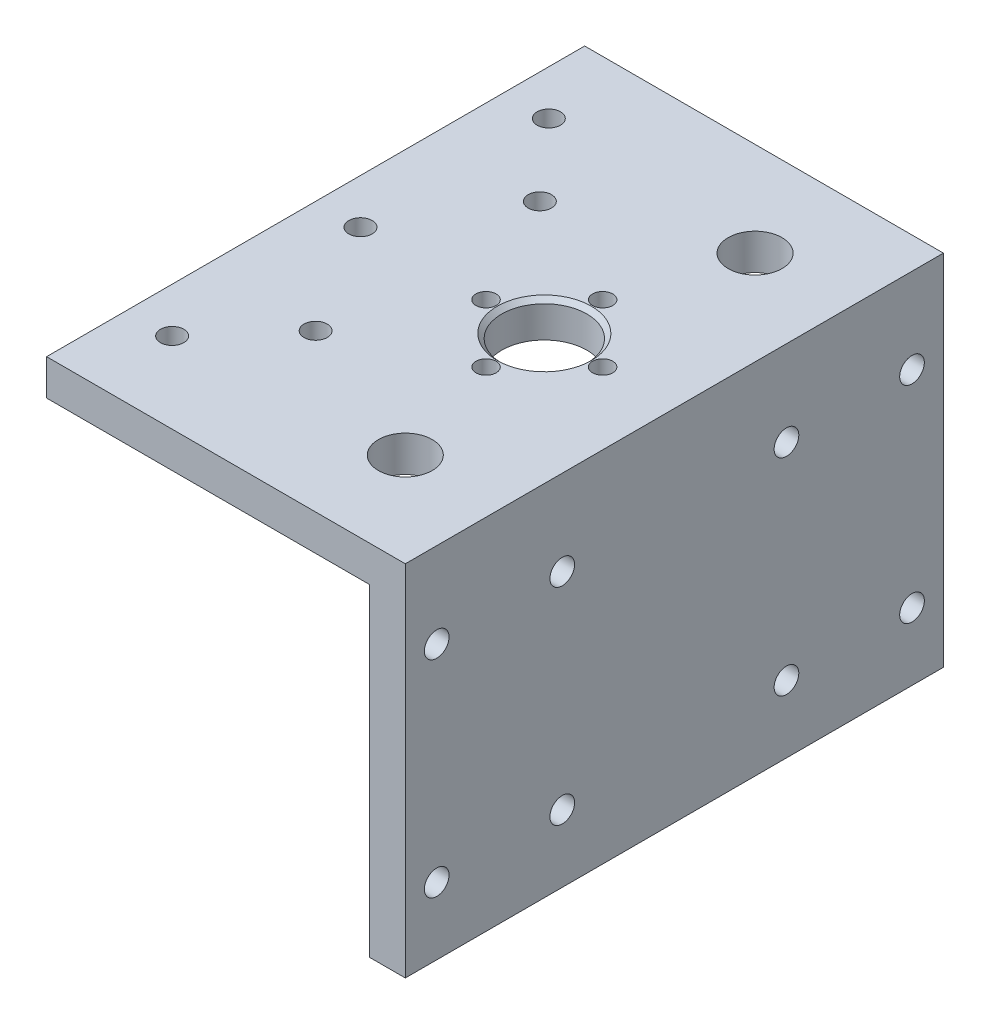
SolidWorks part; units mm, degrees
material "Lega 1060"
ref_plane "Piano frontale" through (0, 0, 0) normal (0, 0, 1) x (1, 0, 0)
ref_plane "Piano superiore" through (0, 0, 0) normal (0, 1, 0) x (1, 0, 0)
ref_plane "Piano destro" through (0, 0, 0) normal (1, 0, 0) x (0, 0, -1)
sketch "Schizzo1" plane through (0, 0, 0) normal (0, 0, 1) x (1, 0, 0)
  line L0 (0, 0) -> (-80, 0)
  line L1 (-80, 0) -> (-80, -8)
  line L2 (-80, -8) -> (-8, -8)
  line L3 (-8, -8) -> (-8, -80)
  line L4 (-8, -80) -> (0, -80)
  line L5 (0, -80) -> (0, 0)
  dimension "D1" = 80
  dimension "D2" = 80
  dimension "D3" = 8
  dimension "D4" = 8
extrude "Estrusione-Estrusione1" add sketch "Schizzo1" along normal blind 120
sketch "Schizzo12" plane through (0, 0, 0) normal (1, 0, 0) x (0, 0, -1)
  line L0 (0, -8) -> (-120, -8) construction
  line L1 (-21, 0) -> (-21, 18.8536) construction
  line L5 (0, -80) -> (0, 0) construction
  line L6 (-120, -80) -> (-120, 0) construction
  line L7 (-120, 0) -> (0, 0) construction
  line L8 (-113, -19) -> (10.4492, -19) construction
  line L9 (-113, -65) -> (16.1501, -65) construction
  line L10 (-99, -47.4454) -> (-99, 40.839) construction
  circle A0 centre (-113, -19) radius 2.75
  circle A1 centre (-85, -19) radius 2.75
  circle A6 centre (-35, -19) radius 2.75
  circle A7 centre (-7, -19) radius 2.75
  circle A10 centre (-85, -65) radius 2.75
  circle A11 centre (-113, -65) radius 2.75
  circle A12 centre (-7, -65) radius 2.75
  circle A13 centre (-35, -65) radius 2.75
  dimension "D1" = 5.5
  dimension "D5" = 28
  dimension "D6" = 28
  dimension "D7" = 28
  dimension "D8" = 28
  dimension "D2" = 8
  dimension "D3" = 11
  dimension "D4" = 57
  dimension "D9" = 21
  dimension "D10" = 21
sketch "Schizzo6" plane through (0, 0, 0) normal (0, 1, 0) x (1, 0, 0)
  line L0 (-21, -0.5808) -> (-21, -110.5835) construction
  line L2 (0, 0) -> (-80, 0) construction
  line L3 (-32.5218, -60) -> (-8.0464, -60) construction
  line L6 (0, -120) -> (-80, -120) construction
  circle A0 centre (-21, -21) radius 6
  circle A1 centre (-21, -99) radius 6
  dimension "D2" = 12
  dimension "D1" = 13
  dimension "D3" = 21
extrude "Taglio-Estrusione2" cut sketch "Schizzo6" against normal up to next
sketch "Schizzo7" plane through (0, 0, 0) normal (0, 1, 0) x (1, 0, 0)
  line L0 (-53.636, -60) -> (3.6289, -60) construction
  line L1 (0, -120) -> (-80, -120) construction
  line L2 (0, 0) -> (-80, 0) construction
  line L3 (-21, -21) -> (-21, -99) construction
  circle A0 centre (-29, -60) radius 9.5
  dimension "D1" = 19
  dimension "D2" = 8
extrude "Taglio-Estrusione3" cut sketch "Schizzo7" against normal up to next
hole_wizard "Foro per Vite M4-2" positions "Schizzo9" profile "Schizzo8" hole size "M4" standard "ISO" end condition through all
sketch "Schizzo9" plane through (0, 0, 0) normal (0, 1, 0) x (1, 0, 0)
  line L0 (-18.4657, -60) -> (-16, -60) construction
  line L2 (-29, -57.7684) -> (-29, -66.5063) construction
  circle A2 centre (-29, -60) radius 9.5 construction
  point P0 (-29, -47)
  point P2 (-42, -60)
  point P4 (-29, -73)
  point P8 (-16, -60)
  point P20 (-29, -60)
  dimension "D1" = 26
  dimension "D2" = 13
  dimension "D3" = 13
sketch "Schizzo8" plane through (-29, 0, 47) normal (1, 0, 0) x (0, 0, 1)
  line L0 (0, 0) -> (0, 80)
  line L1 (0, 80) -> (2.25, 80)
  line L2 (2.25, 80) -> (2.25, 0)
  line L5 (2.25, 0) -> (0, 0)
  line L11 (0, -6.35) -> (0, 107.95) construction
  dimension "Thru Hole Dia." = 4.5
  dimension "Thru Hole Depth" = 80
extrude "Taglio-Estrusione4" cut sketch "Schizzo12" against normal blind 10
sketch "Schizzo14" plane through (0, 0, 0) normal (0, 1, 0) x (1, 0, 0)
  line L0 (-70, 0) -> (-70, -120) construction
  line L1 (0, 0) -> (-80, 0) construction
  line L2 (0, -120) -> (-80, -120) construction
  line L3 (-80, -120) -> (-80, 0) construction
  line L4 (-55, 0) -> (-55, -120) construction
  line L5 (-21, -99) -> (-80, -99) construction
  line L6 (-80, -60) -> (0, -60) construction
  line L7 (0, -120) -> (0, 0) construction
  line L8 (-21, -21) -> (-80, -21) construction
  circle A0 centre (-70, -18) radius 2.6
  circle A1 centre (-70, -60) radius 2.6
  circle A2 centre (-70, -102) radius 2.6
  circle A3 centre (-55, -35) radius 2.6
  circle A4 centre (-55, -85) radius 2.6
  dimension "D3" = 5.2
  dimension "D4" = 5.2
  dimension "D5" = 5.2
  dimension "D6" = 5.2
  dimension "D7" = 5.2
  dimension "D1" = 10
  dimension "D2" = 25
  dimension "D8" = 35
  dimension "D9" = 35
  dimension "D10" = 25
  dimension "D11" = 42
extrude "Taglio-Estrusione5" cut sketch "Schizzo14" against normal blind 10
chamfer "Smusso2" distance 1 angle 45 1 edges at (-38.5, 0, 60)
